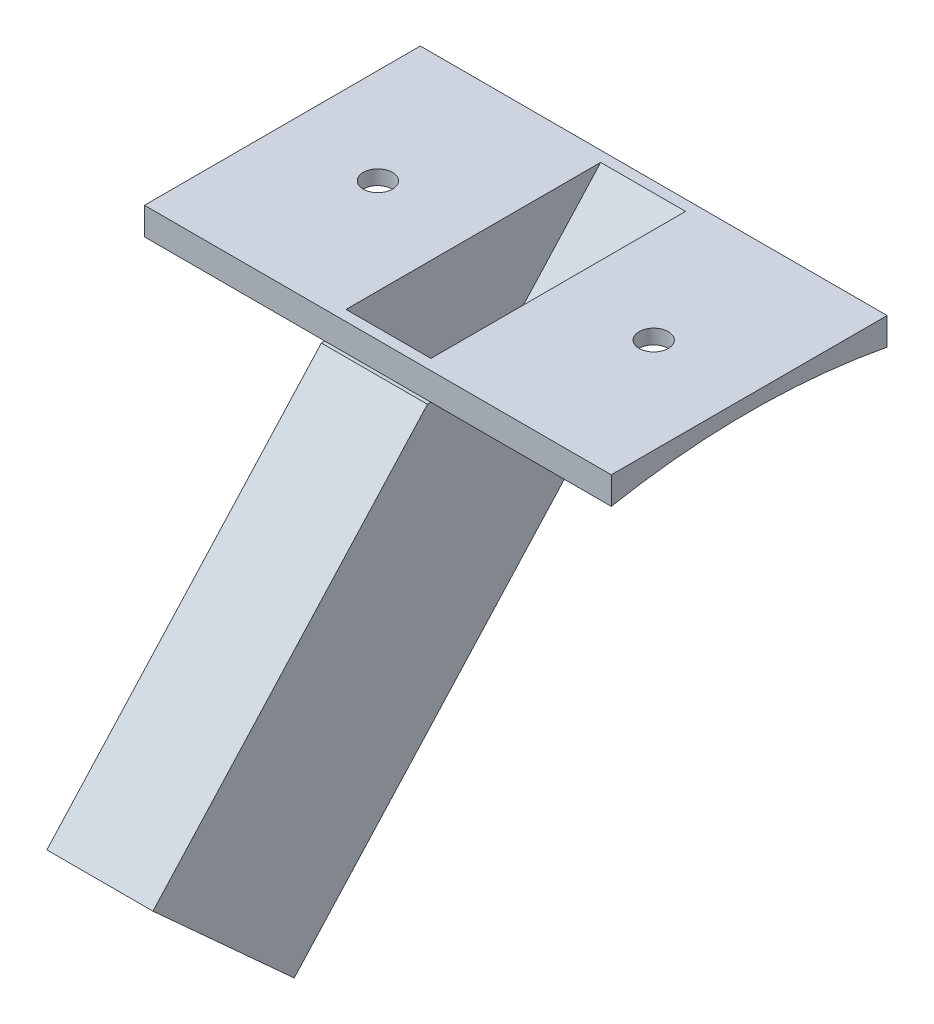
SolidWorks part; units mm, degrees
other "Markup1"
sketch "Sketch5" plane through (22, 10, -8) normal (0.0288, 0.9967, -0.0756) x (0.9789, -0.0434, -0.1997)
sketch "Sketch14" plane through (19, 36, -27) normal (0.0288, 0.9967, -0.0756) x (0.9789, -0.0434, -0.1997)
sketch "Sketch15" plane through (19, 36, -27) normal (0.0288, 0.9967, -0.0756) x (0.9789, -0.0434, -0.1997)
sketch "Sketch17" plane through (19, 36, -27) normal (0.0288, 0.9967, -0.0756) x (0.9789, -0.0434, -0.1997)
ref_plane "Front Plane" through (0, 0, 0) normal (0, 0, 1) x (1, 0, 0)
ref_plane "Top Plane" through (0, 0, 0) normal (0, 1, 0) x (1, 0, 0)
ref_plane "Right Plane" through (0, 0, 0) normal (1, 0, 0) x (0, 0, -1)
sketch "Sketch18" plane through (0, 0, 0) normal (0, 1, 0) x (1, 0, 0)
  line L1 (0, 0) -> (18, 0)
  line L2 (0, 0) -> (0, 26)
  line L3 (0, 26) -> (18, 26)
  line L4 (18, 0) -> (18, 26)
  circle A0 centre (9, 13) radius 1.375
  dimension "D3" = 2.75
  dimension "D4" = 9
  dimension "D5" = 13
  dimension "D1" = 26
  dimension "D2" = 18
extrude "Boss-Extrude1" add sketch "Sketch18" along normal blind 2.58
sketch "Sketch19" plane through (18, 0, 0) normal (1, 0, 0) x (0, 0, -1)
  line L0 (0, 0) -> (26, 0) construction
  line L1 (0, 2.58) -> (1, 2.58)
  line L2 (0, 2.58) -> (0, 0)
  line L3 (0, 0) -> (1, 0)
  line L4 (1, 2.58) -> (1, 0)
  line L6 (26, 2.58) -> (25, 2.58)
  line L7 (26, 2.58) -> (26, 0)
  line L8 (26, 0) -> (25, 0)
  line L9 (25, 2.58) -> (25, 0)
  dimension "D1" = 1
  dimension "D2" = 1
extrude "Boss-Extrude2" add sketch "Sketch19" along normal blind 8
sketch "Sketch20" plane through (26, 0, 0) normal (1, 0, 0) x (0, 0, -1)
  line L1 (0, 2.58) -> (26, 2.58)
  line L2 (0, 2.58) -> (0, 0)
  line L3 (0, 0) -> (26, 0)
  line L4 (26, 2.58) -> (26, 0)
extrude "Boss-Extrude3" add sketch "Sketch20" along normal blind 18
sketch "Sketch21" plane through (0, 2.58, 0) normal (0, 1, 0) x (1, 0, 0)
  line L0 (44, 26) -> (0, 26) construction
  line L1 (44, 26) -> (44, 0) construction
  circle A0 centre (35, 13) radius 1.375
  dimension "D1" = 2.75
  dimension "D2" = 13
  dimension "D3" = 9
extrude "Cut-Extrude1" cut sketch "Sketch21" against normal blind 18
sketch "Sketch22" plane through (44, 0, 0) normal (1, 0, 0) x (0, 0, -1)
  circle A0 centre (13, -68.7823) radius 70
ref_plane "Plane1" through (0, 0, -9.5) normal (0, 0, -1) x (-1, 0, 0)
sketch "Sketch26" plane through (26, 0, 0) normal (-1, 0, 0) x (0, 0, 1)
  line L5 (-19.4256, 0) -> (-1, 0)
  line L6 (13.624, -39.8783) -> (25.4595, -29.1117)
  line L7 (-25, 0) -> (-1, 0)
  line L8 (-1, 0) -> (-1, 2.58)
  line L9 (-1, 2.58) -> (-25, 2.58)
  line L10 (-25, 2.58) -> (-25, 0)
  line L11 (-25, 0) -> (-1, 0)
  line L15 (25.4595, -29.1117) -> (26.1993, -28.4387)
  line L16 (25.4595, -29.1117) -> (-1.297, 0.301)
  line L17 (13.624, -39.8783) -> (12.8843, -40.5512)
  line L18 (-21.2807, 0) -> (-19.4256, 0)
  line L19 (0.2201, 0) -> (-1, 0)
  line L20 (-25, 2.58) -> (13.624, -39.8783)
  line L21 (12.8843, -40.5512) -> (-25, 1.0939)
  line L22 (-25, 2.58) -> (-25, 0) construction
  line L23 (26.1993, -28.4387) -> (4.3449, -4.4148)
  line L24 (3.6051, -5.0877) -> (4.3449, -4.4148)
  line L26 (4.3449, -4.4148) -> (0.2201, 0)
  line M8 (-25, 0) -> (-1, 0)
  line M11 (-25, 2.58) -> (-25, 0)
  dimension "D2" = 16
  dimension "D3" = 90
  dimension "D4" = 90
  dimension "D5" = 1
  dimension "D6" = 1
  dimension "D1" = 0
extrude "Boss-Extrude12" add sketch "Sketch26" against normal blind 1 separate body contours L5 M8 region at (26, -17.3875, 3.4166)
extrude "Boss-Extrude13" add sketch "Sketch26<3>" along normal blind 8 and the other way blind 1 contours L21 L17 L20 L11 | L24 L16 L15 L23 | L21 L11 L20 M11 region at (26, -16.7632, 14.9022) region at (26, -20.1079, -5.0388) region at (26, 0.9686, -24.1189)
sketch "Sketch26<3>" plane through (26, 0, 0) normal (-1, 0, 0) x (0, 0, 1) same geometry as "Sketch26"
sketch "Sketch27" plane through (0, -0.5093, -0.5598) normal (0, -0.6729, -0.7397) x (-1, 0, 0)
  line L0 (-26, -38.6666) -> (-26, 0.6885) construction
  line L1 (-18, -38.6666) -> (-26, -38.6666)
  line L2 (-18, -38.6666) -> (-18, -37.6666)
  line L3 (-18, -37.6666) -> (-26, -37.6666)
  line L4 (-26, -38.6666) -> (-26, -37.6666)
  dimension "D1" = 1
extrude "Boss-Extrude14" add sketch "Sketch27" along normal blind 2.5
sketch "Sketch28" plane through (0, -11.276, -12.3953) normal (0, 0.6729, 0.7397) x (1, 0, 0)
  line L0 (26, 15.2436) -> (26, -38.6666) construction
  line L1 (18, -38.6666) -> (26, -38.6666)
  line L2 (18, -38.6666) -> (18, -37.6666)
  line L3 (18, -37.6666) -> (26, -37.6666)
  line L4 (26, -38.6666) -> (26, -37.6666)
  dimension "D1" = 1
extrude "Boss-Extrude15" add sketch "Sketch28" along normal blind 2.5
sketch "Sketch29" plane through (18, 0, 0) normal (-1, 0, 0) x (0, 0, 1)
  line L0 (-24.0049, 0) -> (12.8843, -40.5512)
  line L1 (12.8843, -40.5512) -> (26.1993, -28.4387)
  line L2 (26.1993, -28.4387) -> (0.3287, 0)
  line L3 (-24.0049, 0) -> (0.3287, 0)
extrude "Boss-Extrude16" add sketch "Sketch29" along normal blind 1
sketch "Sketch31" plane through (17, 0, 0) normal (-1, 0, 0) x (0, 0, 1)
  circle A0 centre (-13, -68.7823) radius 70
sketch "Sketch32" plane through (18, 0, 0) normal (1, 0, 0) x (0, 0, -1)
  line L0 (-4.3449, -4.4148) -> (-3.6051, -5.0877)
  line L1 (-3.6051, -5.0877) -> (1.0231, 0)
  line L2 (0, 0) -> (26, 0) construction
  line L3 (1.0231, 0) -> (24.0049, 0) construction
  line L4 (1.0231, 0) -> (-0.3287, 0)
  line L5 (-4.3449, -4.4148) -> (-0.3287, 0) construction
  line L6 (-0.3287, 0) -> (-4.3449, -4.4148)
extrude "Boss-Extrude17" add sketch "Sketch32" along normal blind 9
extrude "Cut-Extrude8" cut sketch "Sketch31" along normal blind 17
extrude "Cut-Extrude9" cut sketch "Sketch22" against normal blind 17
